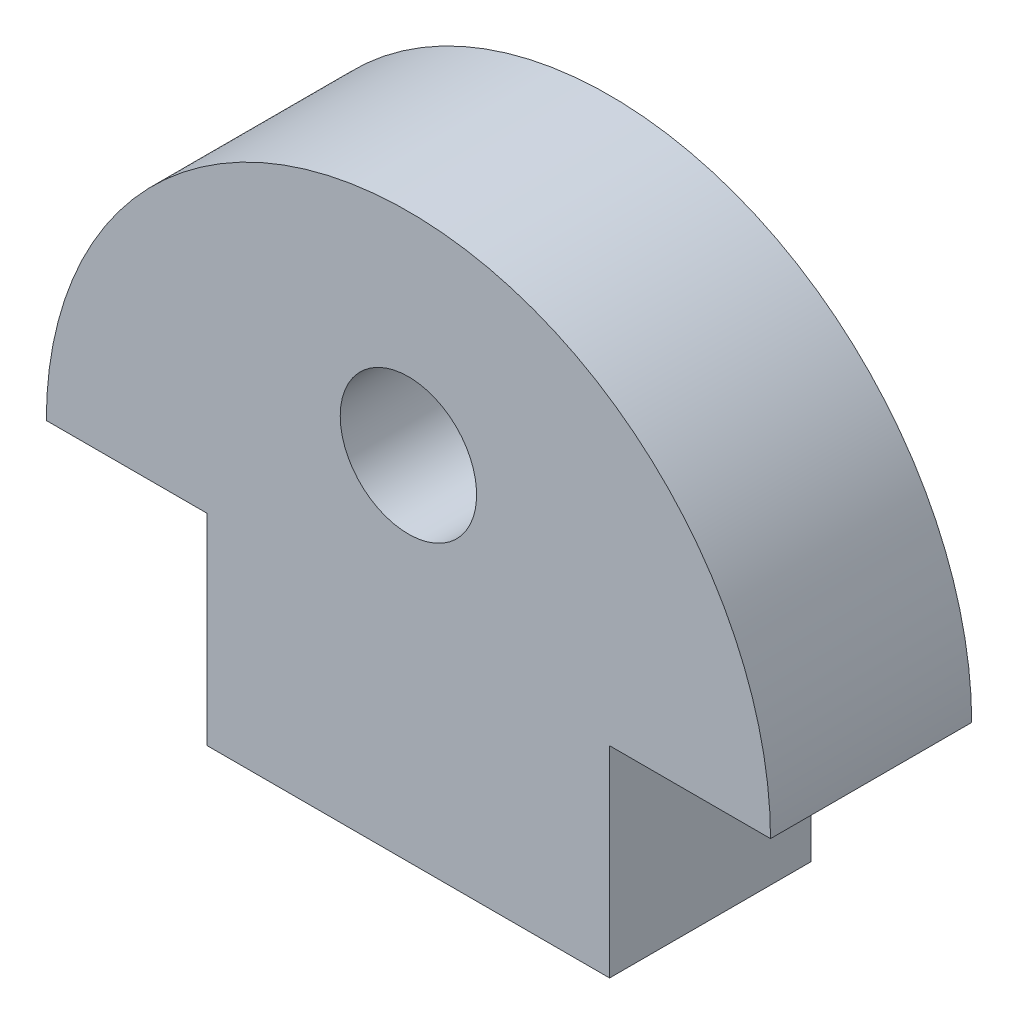
SolidWorks part; units mm, degrees
material "Custom Plastic"
ref_plane "Front Plane" through (0, 0, 0) normal (0, 0, 1) x (1, 0, 0)
ref_plane "Top Plane" through (0, 0, 0) normal (0, 1, 0) x (1, 0, 0)
ref_plane "Right Plane" through (0, 0, 0) normal (1, 0, 0) x (0, 0, -1)
sketch "Sketch1" plane through (0, 0, 0) normal (0, 0, 1) x (1, 0, 0)
  line L1 (-11.43, -12.7) -> (11.43, -12.7)
  line L2 (-11.43, -12.7) -> (-11.43, 12.7) construction
  line L3 (-11.43, 12.7) -> (11.43, 12.7) construction
  line L4 (11.43, -12.7) -> (11.43, 12.7) construction
  line L5 (-11.43, -12.7) -> (11.43, 12.7) construction
  line L6 (-11.43, 12.7) -> (11.43, -12.7) construction
  arc A0 (-11.43, -12.7) -> (11.43, -12.7) centre (0, -12.7) cw
  point P0 (0, 0)
  dimension "D1" = 22.86
  dimension "D2" = 25.4
extrude "Base" add sketch "Sketch1" along normal blind 6.35
sketch "Axle hole placement" plane through (0, 0, 6.35) normal (0, 0, 1) x (1, 0, 0)
  line L0 (-11.43, -7.9375) -> (11.43, -7.9375) construction
  line L3 (0, -1.27) -> (0, -12.7) construction
  line L4 (-11.43, -12.7) -> (11.43, -12.7) construction
  line L5 (-11.43, -12.7) -> (11.43, -12.7) construction
  line L7 (-11.43, -12.7) -> (11.43, -12.7) construction
  arc A0 (11.43, -12.7) -> (-11.43, -12.7) centre (0, -12.7) ccw construction
  point P12 (0, -7.9375)
  dimension "D1" = 4.7625
hole_wizard "Axle hole" positions "Sketch5" profile "Sketch4" hole size "#8" standard "ANSI Inch" end condition through all
sketch "Sketch5" plane through (0, 0, 0) normal (0, 0, -1) x (-1, 0, 0)
  point P3 (0, -7.9375)
sketch "Sketch4" plane through (0, -7.9375, 0) normal (1, 0, 0) x (0, 1, 0)
  line L0 (0, 0) -> (0, 6.35)
  line L1 (0, 6.35) -> (2.1526, 6.35)
  line L2 (2.1526, 6.35) -> (2.1526, 0)
  line L5 (2.1526, 0) -> (0, 0)
  line L11 (0, -6.35) -> (0, 107.95) construction
  dimension "Thru Hole Dia." = 4.3053
  dimension "Thru Hole Depth" = 6.35
sketch "Sketch8" plane through (0, 0, 6.35) normal (0, 0, 1) x (1, 0, 0)
  line L0 (-11.43, -12.7) -> (11.43, -12.7) construction
  line L1 (-6.35, -12.7) -> (6.35, -12.7)
  line L2 (-6.35, -12.7) -> (-6.35, -19.05)
  line L3 (-6.35, -19.05) -> (6.35, -19.05)
  line L4 (6.35, -12.7) -> (6.35, -19.05)
  point P6 (0, -12.7)
  dimension "D1" = 12.7
  dimension "D2" = 6.35
extrude "Boss-Extrude2" add sketch "Sketch8" against normal blind 6.35
equation "\"MAT_THICKNESS\"=0.25"
equation "\"D1@Base\"=\"MAT_THICKNESS\""
equation "\"D2@Sketch8\"=\"MAT_THICKNESS\""
equation "\"D1@Boss-Extrude2\"=\"MAT_THICKNESS\""
